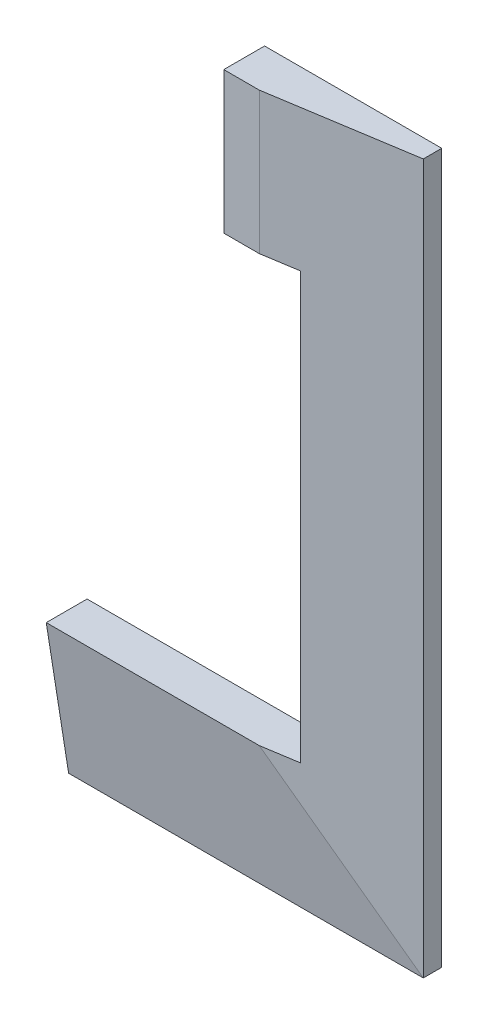
SolidWorks part; units mm, degrees
ref_plane "Płaszczyzna przednia" through (0, 0, 0) normal (0, 0, 1) x (1, 0, 0)
ref_plane "Płaszczyzna górna" through (0, 0, 0) normal (0, 1, 0) x (1, 0, 0)
ref_plane "Płaszczyzna prawa" through (0, 0, 0) normal (1, 0, 0) x (0, 0, -1)
sketch "Szkic2" plane through (0, 0, 0) normal (0, 0, 1) x (1, 0, 0)
  line L0 (18.5428, 83.2454) -> (18.5428, 43.3454)
  line L1 (-81.3572, 83.2454) -> (18.5428, 83.2454)
  line L2 (-81.3572, 83.2454) -> (-81.3572, -116.5546)
  line L3 (-81.3572, -116.5546) -> (18.5428, -116.5546)
  line L5 (-51.4572, 43.3454) -> (18.5428, 43.3454)
  line L6 (-51.4572, 43.3454) -> (-51.4572, -76.6546)
  line L7 (-51.4572, -76.6546) -> (18.5428, -76.6546)
  line L9 (-51.4572, -16.6546) -> (-81.3572, -16.6546) construction
  line L10 (18.5428, 43.3454) -> (18.5428, 83.2454) construction
  line L11 (18.5428, -76.6546) -> (18.5428, -116.5546) construction
  line L12 (18.5428, -76.6546) -> (18.5428, -116.5546)
  dimension "D1" = 199.8
  dimension "D3" = 120
  dimension "D4" = 29.9
extrude "Dodanie-wyciągnięcie1" add sketch "Szkic2" along normal blind 5.2
ref_plane "Płaszczyzna1" through (0, 0, 11.5) normal (0, 0, 1) x (1, 0, 0)
sketch "Szkic3" plane through (0, 0, 11.5) normal (0, 0, 1) x (1, 0, 0)
  line L5 (18.5428, -76.6546) -> (-51.4572, -76.6546) construction
  line L6 (-41.4572, -76.6546) -> (18.5428, -76.6546)
  line L12 (-41.4572, -76.6546) -> (-41.4572, 83.2454)
  line L13 (18.5428, 83.2454) -> (-81.3572, 83.2454) construction
  line L14 (-41.4572, 83.2454) -> (18.5428, 83.2454)
  line L15 (18.5428, 83.2454) -> (18.5428, -76.6546)
sketch "Szkic5" plane through (0, 0, 5.2) normal (0, 0, 1) x (1, 0, 0)
  line L1 (-81.3572, 83.2454) -> (18.5428, 83.2454)
  line L2 (-81.3572, 83.2454) -> (-81.3572, -116.5546)
  line L3 (-81.3572, -116.5546) -> (18.5428, -116.5546)
  line L4 (18.5428, 83.2454) -> (18.5428, -116.5546)
loft "Wyciągnięcie po profilach3" add profiles "Szkic3", "Szkic5" connector at (18.5428, 83.2454, 11.5) connector at (18.5428, 83.2454, 5.2)
sketch "Szkic6" plane through (-51.4572, 0, 0) normal (1, 0, 0) x (0, 0, -1)
  line L1 (0, 43.3454) -> (-49.2712, 43.3454)
  line L2 (0, 43.3454) -> (0, -76.6546)
  line L3 (0, -76.6546) -> (-49.2712, -76.6546)
  line L4 (-49.2712, 43.3454) -> (-49.2712, -76.6546)
extrude "Wytnij-wyciągnięcie1" cut sketch "Szkic6" along normal blind 78
sketch "Szkic7" plane through (-51.4572, 0, 0) normal (1, 0, 0) x (0, 0, -1)
  line L0 (-5.12, -76.6546) -> (-5.12, -36.5546) construction
  line L2 (-5.12, -36.5546) -> (-5.12, 3.2454) construction
  line L3 (-5.12, 3.2454) -> (-5.12, 43.3454) construction
  line L5 (0, -76.6546) -> (0, 43.3454) construction
  line L7 (-5.12, -34.1298) -> (-7.22, -35.3422)
  line L8 (-7.22, -35.3422) -> (-7.22, -37.7671)
  line L9 (-7.22, -37.7671) -> (-5.12, -38.9795)
  line L10 (-5.12, -38.9795) -> (-3.02, -37.7671)
  line L11 (-3.02, -37.7671) -> (-3.02, -35.3422)
  line L12 (-3.02, -35.3422) -> (-5.12, -34.1298)
  line L13 (-5.12, 5.6702) -> (-7.22, 4.4578)
  line L14 (-7.22, 4.4578) -> (-7.22, 2.0329)
  line L15 (-7.22, 2.0329) -> (-5.12, 0.8205)
  line L16 (-5.12, 0.8205) -> (-3.02, 2.0329)
  line L17 (-3.02, 2.0329) -> (-3.02, 4.4578)
  line L18 (-3.02, 4.4578) -> (-5.12, 5.6702)
  circle A0 centre (-5.12, -36.5546) radius 2.1 construction
  circle A1 centre (-5.12, 3.2454) radius 2.1 construction
  dimension "D2" = 4.2
  dimension "D3" = 4.2
  dimension "D1" = 5.12
extrude "Wytnij-wyciągnięcie2" cut sketch "Szkic7" against normal blind 5.6
sketch "Szkic9" plane through (-51.4572, 0, 0) normal (1, 0, 0) x (0, 0, -1)
  circle A0 centre (-5.12, 3.2454) radius 2.4249
  circle A1 centre (-5.12, -36.5546) radius 2.4249
  circle A2 centre (-5.12, 3.2454) radius 1.2
  circle A3 centre (-5.12, -36.5546) radius 1.2
extrude "Dodanie-wyciągnięcie3" add sketch "Szkic9" against normal blind 3.8
sketch "Szkic10" plane through (0, 0, 11.5) normal (0, 0, 1) x (1, 0, 0)
  line L0 (-41.4572, 83.2454) -> (-41.4572, 43.3454) construction
  line L1 (-31.4572, 83.2454) -> (18.5428, 83.2454)
  line L2 (-31.4572, 83.2454) -> (-31.4572, 43.3454)
  line L3 (-31.4572, 43.3454) -> (18.5428, 43.3454)
  line L4 (18.5428, 83.2454) -> (18.5428, 43.3454)
  dimension "D1" = 10
extrude "Wytnij-wyciągnięcie4" cut sketch "Szkic10" against normal blind 24
mirror "Lustro1" about plane through (18.5428, 83.2454, 5.2) normal (-1, 0, 0) of bodies 128
move or copy body "Obiekt-Przenieś/Kopiuj1" bodies to move or copy 129 copy no translate (34.8901, 0, 0) parameters "D1"=34.8901, "D2"=0, "D3"=0
delete or keep bodies "Obiekt-Usuń/zachowaj 1" type delete bodies bodies 128
